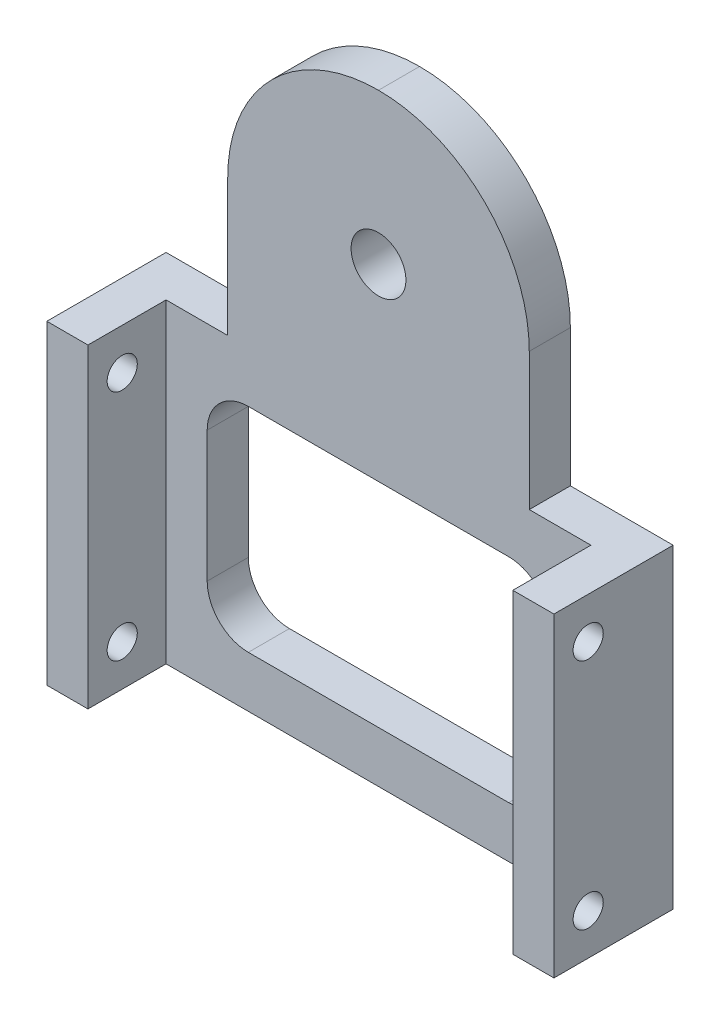
SolidWorks part; units mm, degrees
ref_plane "Front Plane" through (0, 0, 0) normal (0, 0, 1) x (1, 0, 0)
ref_plane "Top Plane" through (0, 0, 0) normal (0, 1, 0) x (1, 0, 0)
ref_plane "Right Plane" through (0, 0, 0) normal (1, 0, 0) x (0, 0, -1)
sketch "Sketch1" plane through (0, 0, 0) normal (0, 0, 1) x (1, 0, 0)
  line L0 (-11, 11.5) -> (-18.5, 11.5)
  line L1 (18.5, 11.5) -> (11, 11.5)
  line L2 (18.5, 11.5) -> (18.5, -11.5)
  line L3 (18.5, -11.5) -> (-18.5, -11.5)
  line L4 (-18.5, 11.5) -> (-18.5, -11.5)
  line L5 (18.5, 11.5) -> (-18.5, -11.5) construction
  line L6 (18.5, -11.5) -> (-18.5, 11.5) construction
  line L7 (-18.5, 11.5) -> (-15.5, 11.5)
  line L8 (-18.5, 11.5) -> (-18.5, -11.5)
  line L9 (-18.5, -11.5) -> (-15.5, -11.5)
  line L10 (-15.5, 11.5) -> (-15.5, -11.5)
  line L11 (18.5, 11.5) -> (15.5, 11.5)
  line L12 (18.5, 11.5) -> (18.5, -11.5)
  line L13 (18.5, -11.5) -> (15.5, -11.5)
  line L14 (15.5, 11.5) -> (15.5, -11.5)
  line L16 (-11, 11.5) -> (-11, 32.5)
  line L17 (-11, 32.5) -> (11, 32.5)
  line L18 (11, 11.5) -> (11, 32.5)
  line L20 (-12.5, 7.7703) -> (12.5, 7.7703)
  line L21 (-12.5, 7.7703) -> (-12.5, -7.7703)
  line L22 (-12.5, -7.7703) -> (12.5, -7.7703)
  line L23 (12.5, 7.7703) -> (12.5, -7.7703)
  line L24 (-12.5, 7.7703) -> (12.5, -7.7703) construction
  line L25 (-12.5, -7.7703) -> (12.5, 7.7703) construction
  circle A0 centre (0, 21.5) radius 2
  point P0 (0, 0)
  point P14 (0, -11.5)
  point P15 (0, 32.5)
  point P18 (0, 0)
  dimension "D10" = 4
  dimension "D1" = 31
  dimension "D2" = 3
  dimension "D3" = 3
  dimension "D4" = 22
  dimension "D5" = 23
  dimension "D6" = 10
  dimension "D7" = 11
  dimension "D8" = 6
extrude "Boss-Extrude1" add sketch "Sketch1" along normal blind 3 contours L1 L18 L17 L16 L0 L10 L3 L14 A0 region at (0, 12.784, 0)
extrude "Boss-Extrude2" add sketch "Sketch1<4>" along normal blind 8.7 contours L1 L14 L3 L2 | L10 L0 L4 L3 region at (-17, 0, 0) region at (17, 0, 0)
sketch "Sketch1<4>" plane through (0, 0, 0) normal (0, 0, 1) x (1, 0, 0) same geometry as "Sketch1"
sketch "Sketch2" plane through (18.5, 0, 0) normal (1, 0, 0) x (0, 0, -1)
  line L0 (-8.7, 11.5) -> (0, 11.5) construction
  line L1 (-8.7, 11.5) -> (-8.7, -11.5) construction
  circle A0 centre (-6.2, 8.5) radius 1.1
  circle A1 centre (-6.2, -8.5) radius 1.1
  dimension "D1" = 2.2
  dimension "D2" = 3
  dimension "D3" = 2.5
  dimension "D4" = 17
extrude "Cut-Extrude1" cut sketch "Sketch2" against normal up to surface (37 mm away) up to face at (-18.5, 0, 4.35)
sketch "Sketch3" plane through (0, 0, 0) normal (0, 0, -1) x (-1, 0, 0)
  circle A0 centre (0, 21.5) radius 2.5
  circle A1 centre (0, 21.5) radius 2 construction
  circle M2 centre (0, 21.5) radius 2
  dimension "D1" = 0.5
extrude "Boss-Extrude4" add sketch "Sketch3" along normal blind 0.5 contours A0 M2 region at (2.4293, 21.5, 0)
fillet "Fillet1" radius 11 2 edges at (-11, 32.5, 1.5) (11, 32.5, 1.5)
fillet "Fillet2" radius 3 4 edges at (-12.5, 7.7703, 1.5) (-12.5, -7.7703, 1.5) (12.5, -7.7703, 1.5) (12.5, 7.7703, 1.5)
